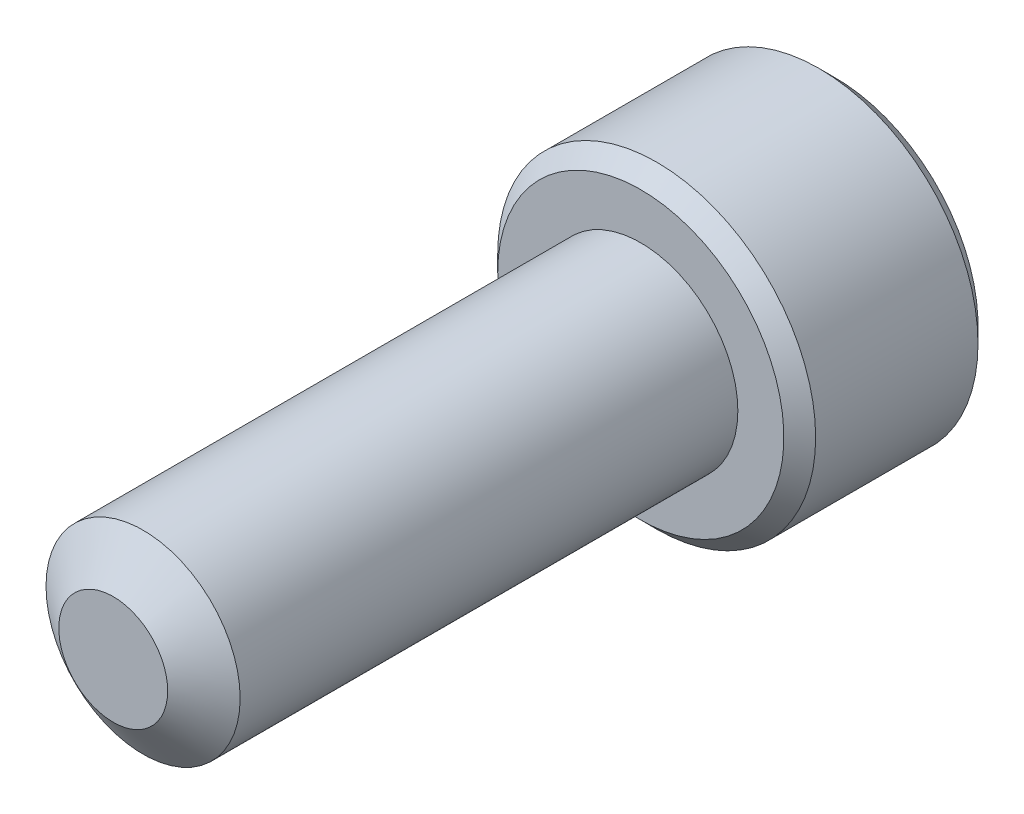
SolidWorks part; units mm, degrees
material "Alloy Steel"
ref_plane "Front Plane" through (0, 0, 0) normal (0, 0, 1) x (1, 0, 0)
ref_plane "Top Plane" through (0, 0, 0) normal (0, 1, 0) x (1, 0, 0)
ref_plane "Right Plane" through (0, 0, 0) normal (1, 0, 0) x (0, 0, -1)
sketch "Sketch1" plane through (0, 0, 0) normal (0, 0, 1) x (1, 0, 0)
  circle A0 centre (0, 0) radius 1.7526
  dimension "OD" = 3.5052
extrude "Extrude1" add sketch "Sketch1" against normal blind 9.525
sketch "Sketch2" plane through (0, 0, 0) normal (0, 0, 1) x (1, 0, 0)
  circle A0 centre (0, 0) radius 1.7526 construction
  circle A1 centre (0, 0) radius 1.7526
curve "Helix/Spiral1" pitch 0.7937 height 10.3188 turns 13 parameters "pitch"=0.7937
sketch "Sketch3" plane through (0, 0, 0) normal (1, 0, 0) x (0, 0, -1)
  line L0 (-0.6945, 1.7526) -> (-0.3969, 1.237)
  line L1 (-0.3969, 1.237) -> (-0.2977, 1.237)
  line L2 (-0.2977, 1.237) -> (0, 1.7526)
  line L3 (-0.6945, 1.7526) -> (0, 1.7526)
  line L4 (-0.3473, 1.7526) -> (-0.3473, 1.237) construction
  line L5 (-0.5457, 1.4948) -> (-0.1488, 1.4948) construction
  line L6 (0, 1.7526) -> (0, -1.7526) construction
  dimension "D1" = 0.0992
  dimension "D2" = 0.3969
  dimension "D3" = 60
sweep "Cut-Sweep1" [suppressed] cut profiles "Sketch3" path "Helix/Spiral1"
sketch "Sketch4" plane through (0, 0, 0) normal (1, 0, 0) x (0, 0, -1)
  line L0 (0.5388, 1.7526) -> (0, 0.983)
  line L1 (0, 0.983) -> (0, 1.7526)
  line L2 (0.5388, 1.7526) -> (0, 1.7526)
  line L3 (-0.6945, 1.7526) -> (0, 1.7526) construction
  line L4 (0, 0) -> (7.0209, 0) construction
  dimension "D1" = 55
  dimension "D2" = 0.254
revolve "Cut-Revolve1" cut sketch "Sketch4" angle 360 about L4
sketch "Sketch5" [suppressed] plane through (0, 0, 0) normal (1, 0, 0) x (0, 0, -1)
  line L0 (9.525, -1.2539) -> (9.525, 1.2505) construction
  line L1 (9.525, 1.8796) -> (87.4327, 1.8796)
  line L2 (9.525, 1.8796) -> (9.525, 0)
  line L3 (9.525, 0) -> (87.3125, 0)
  line L4 (87.3125, 1.5494) -> (87.3125, 0)
  line L5 (87.4327, 1.8796) -> (87.3125, 1.5494)
  line L6 (0, 0) -> (9.9695, 0) construction
  point P3 (87.3125, 1.8796)
  point P10 (87.3125, 1.8796)
  dimension "D1" = 0.3302
  dimension "Thread min" = 87.3125
  dimension "D2" = 0.127
  dimension "D3" = 20
revolve "partially thread" [suppressed] add sketch "Sketch5" angle 360 about L6
sketch "Sketch6" plane through (0, 0, -9.525) normal (0, 0, -1) x (-1, 0, 0)
  circle A0 centre (0, 0) radius 2.8702
  dimension "head dia" = 5.7404
extrude "Extrude2" add sketch "Sketch6" along normal blind 3.5052
sketch "Sketch7" plane through (0, 0, -13.0302) normal (0, 0, -1) x (-1, 0, 0)
  line L1 (0, 1.604) -> (-1.3891, 0.802)
  line L2 (-1.3891, 0.802) -> (-1.3891, -0.802)
  line L3 (-1.3891, -0.802) -> (0, -1.604)
  line L4 (0, -1.604) -> (1.3891, -0.802)
  line L5 (1.3891, -0.802) -> (1.3891, 0.802)
  line L6 (1.3891, 0.802) -> (0, 1.604)
  circle A0 centre (0, 0) radius 1.3891 construction
  dimension "hex dia" = 2.7781
extrude "Cut-Extrude1" cut sketch "Sketch7" against normal blind 2.0836
sketch "Sketch8" plane through (0, 0, -13.0302) normal (0, 0, -1) x (-1, 0, 0)
  circle A0 centre (0, 0) radius 1.604
extrude "Cut-Extrude2" cut sketch "Sketch8" against normal through all draft 45
chamfer "Chamfer1" distance 0.287 angle 45 2 edges at (-2.8702, 0, -13.0302) (-2.8702, 0, -9.525)
sketch "Sketch9" plane through (0, 0, 0) normal (1, 0, 0) x (0, 0, -1)
  line L0 (0, 1.7526) -> (0, -1.7526) construction
  line L1 (4.3656, 1.7526) -> (4.3656, -1.7526) construction
  dimension "D1" = 4.3656
equation "\"D3@Helix/Spiral1\" = \"screw length@Extrude1\"+\"pitch@Helix/Spiral1\""
equation "\"D1@Sketch3\" = \"pitch@Helix/Spiral1\"*.125"
equation "\"D2@Sketch3\" = \"pitch@Helix/Spiral1\"*.5"
equation "\"D1@Cut-Extrude1\" = \"hex dia@Sketch7\"*.75"
equation "\"D1@Chamfer1\" = \"head dia@Sketch6\"*.05"
equation "\"D1@Sketch9\" = \"pitch@Helix/Spiral1\"*5.5"
